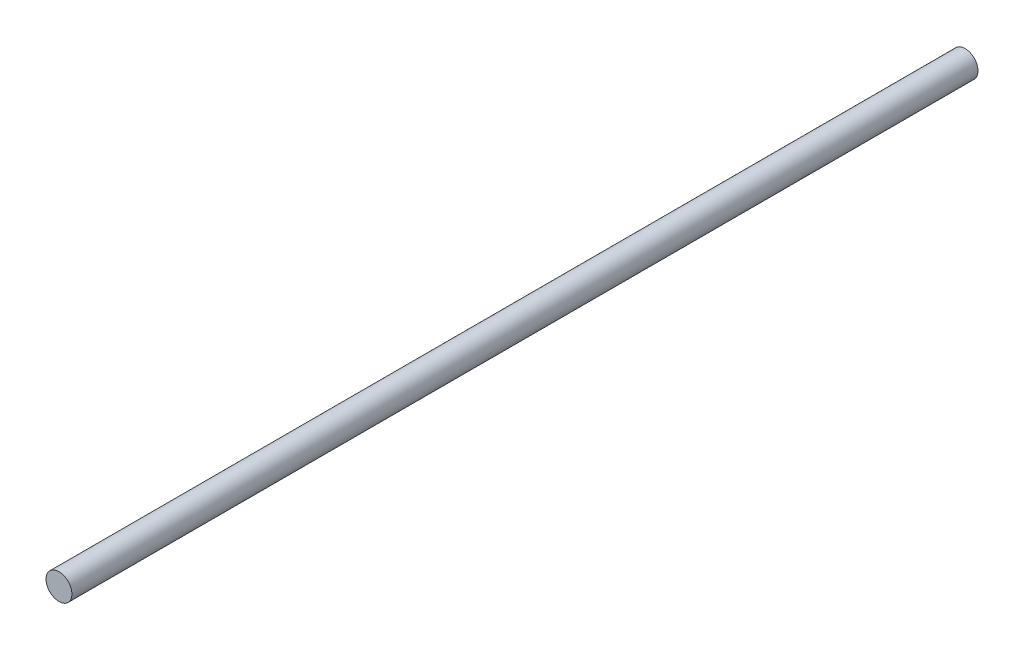
SolidWorks part; units mm, degrees
ref_plane "Front Plane" through (0, 0, 0) normal (0, 0, 1) x (1, 0, 0)
ref_plane "Top Plane" through (0, 0, 0) normal (0, 1, 0) x (1, 0, 0)
ref_plane "Right Plane" through (0, 0, 0) normal (1, 0, 0) x (0, 0, -1)
sketch "Sketch1" plane through (0, 0, 0) normal (0, 1, 0) x (1, 0, 0)
  line L0 (-3.0138, 91.2439) -> (-3.0138, -86.5561)
revolve "Revolve-Thin1" add sketch "Sketch1" angle 360 about L0 wall 2.54
